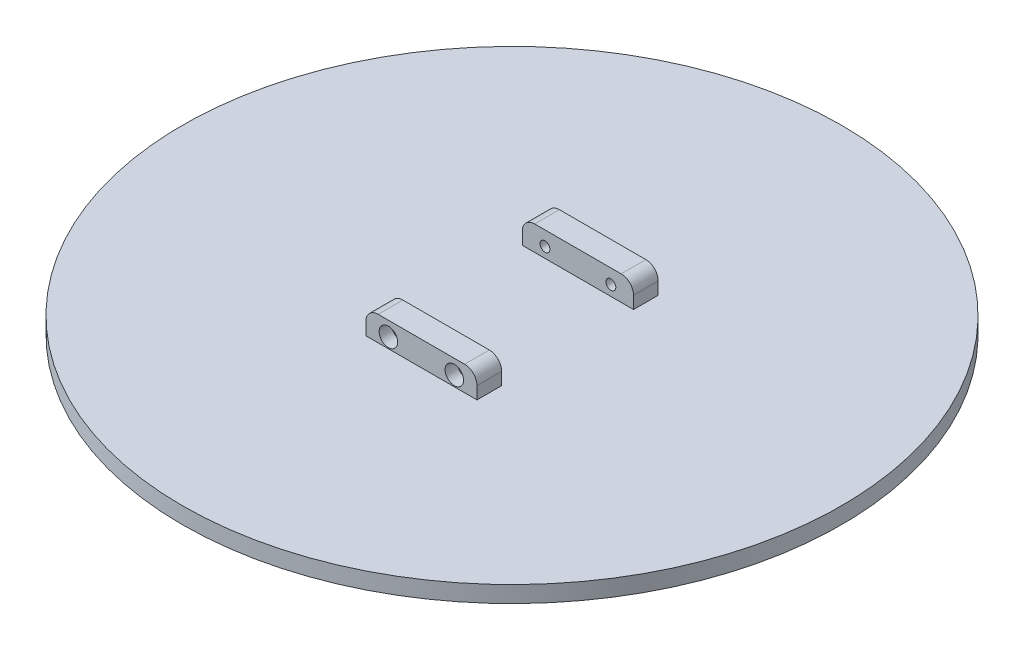
SolidWorks part; units mm, degrees
ref_plane "Front Plane" through (0, 0, 0) normal (0, 0, 1) x (1, 0, 0)
ref_plane "Top Plane" through (0, 0, 0) normal (0, 1, 0) x (1, 0, 0)
ref_plane "Right Plane" through (0, 0, 0) normal (1, 0, 0) x (0, 0, -1)
sketch "Sketch1" plane through (0, 0, 0) normal (0, 1, 0) x (1, 0, 0)
  circle A0 centre (0, 0) radius 32.65
  circle A1 centre (0, 0) radius 37.65
  dimension "D1" = 65.3
  dimension "D2" = 5
extrude "Boss-Extrude1" add sketch "Sketch1" along normal blind 10
sketch "Sketch2" plane through (0, 10, 0) normal (0, 1, 0) x (1, 0, 0)
  circle A0 centre (0, 0) radius 29.65
  circle A1 centre (0, 0) radius 32.65 construction
  circle A2 centre (0, 0) radius 32.65
  dimension "D1" = 3
extrude "Boss-Extrude2" add sketch "Sketch2" against normal blind 4
sketch "Sketch3" plane through (0, 10, 0) normal (0, 1, 0) x (1, 0, 0)
  circle A0 centre (0, 0) radius 80
  dimension "D1" = 160
extrude "Boss-Extrude3" add sketch "Sketch3" along normal blind 4
sketch "Sketch4" plane through (0, 14, 0) normal (0, 1, 0) x (1, 0, 0)
  line L0 (0, 0) -> (-32.7045, 0) construction
  line L1 (-13.5, 16) -> (13.5, 16)
  line L2 (-13.5, 16) -> (-13.5, 22)
  line L3 (-13.5, 22) -> (13.5, 22)
  line L4 (13.5, 16) -> (13.5, 22)
  line L5 (0, 0) -> (0, 16) construction
  dimension "D1" = 6
  dimension "D2" = 32
  dimension "D3" = 27
extrude "Boss-Extrude4" add sketch "Sketch4" along normal blind 6
fillet "Fillet1" radius 3 2 edges at (-13.5, 20, -19) (13.5, 20, -19)
sketch "Sketch6" plane through (0, 0, -22) normal (0, 0, -1) x (-1, 0, 0)
  line L0 (0, 14) -> (0, 20) construction
  line L1 (-13.5, 14) -> (13.5, 14) construction
  line L2 (-10.5, 20) -> (10.5, 20) construction
  circle A0 centre (-8, 16.5) radius 2.25
  circle A1 centre (8, 16.5) radius 2.25
  dimension "D2" = 4.5
  dimension "D1" = 16
  dimension "D3" = 2.5
extrude "Cut-Extrude1" cut sketch "Sketch6" against normal blind 3
hole_wizard "CSK for M2 Countersunk Flat Head Screw1" positions "3DSketch1" profile "Sketch5" countersink size "M2" standard "ISO" end condition through all
sketch3d "3DSketch1"
  line L8 (8, 16.5, -19) -> (8, 16.5, -22) construction
  line L9 (-8, 16.5, -19) -> (-8, 16.5, -22) construction
  point P21 (8, 16.5, -19)
  point P25 (-8, 16.5, -19)
sketch "Sketch5" plane through (8, 16.5, -19) normal (1, 0, 0) x (0, 1, 0)
  line L0 (0, 0) -> (0, 99)
  line L1 (0, 99) -> (1.2, 99)
  line L2 (1.2, 99) -> (1.2, 1)
  line L3 (1.2, 1) -> (2.2, 0)
  line L5 (2.2, 0) -> (0, 0)
  line L6 (-1.2, 1) -> (-2.2, 0) construction
  line L11 (0, -6.35) -> (0, 107.95) construction
  dimension "Thru Hole Dia." = 2.4
  dimension "Thru Hole Depth" = 99
  dimension "Near C'Sink Dia." = 4.4
  dimension "Near C'Sink Angle" = 90
mirror "Mirror1" about plane through (0, 0, 0) normal (0, 0, 1) of "CSK for M2 Countersunk Flat Head Screw1", "Fillet1", "Boss-Extrude4", "Cut-Extrude1"
